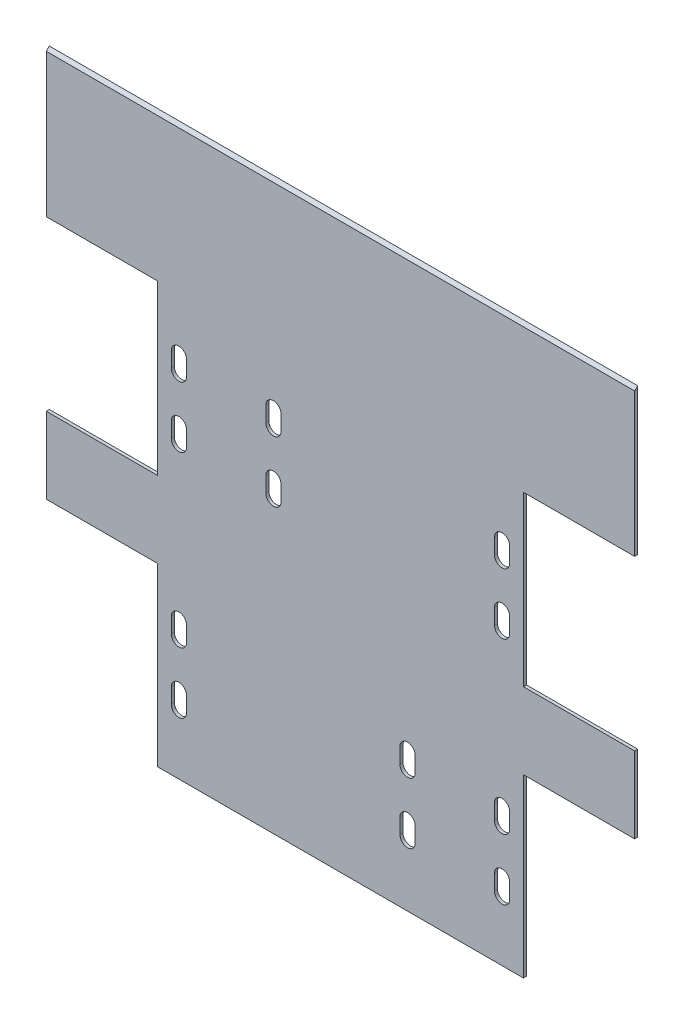
SolidWorks part; units mm, degrees
material "Plain Carbon Steel"
ref_plane "Front Plane" through (0, 0, 0) normal (0, 0, 1) x (1, 0, 0)
ref_plane "Top Plane" through (0, 0, 0) normal (0, 1, 0) x (1, 0, 0)
ref_plane "Right Plane" through (0, 0, 0) normal (1, 0, 0) x (0, 0, -1)
sketch "Sketch1" plane through (0, 0, 0) normal (0, 0, 1) x (1, 0, 0)
  line L1 (-96.5, 72.5) -> (96.5, 72.5)
  line L2 (-96.5, 72.5) -> (-96.5, -72.5)
  line L3 (-96.5, -72.5) -> (96.5, -72.5)
  line L4 (96.5, 72.5) -> (96.5, -72.5)
  line L5 (-96.5, 72.5) -> (96.5, -72.5) construction
  line L6 (-96.5, -72.5) -> (96.5, 72.5) construction
  line L7 (-95, 65.5) -> (-60, 65.5)
  line L8 (-95, 65.5) -> (-95, 5.5)
  line L9 (-95, 5.5) -> (-60, 5.5)
  line L10 (-60, 65.5) -> (-60, 5.5)
  line L11 (-95, 65.5) -> (-60, 5.5) construction
  line L12 (-95, 5.5) -> (-60, 65.5) construction
  line L13 (60, 65.5) -> (95, 65.5)
  line L14 (60, 65.5) -> (60, 5.5)
  line L15 (60, 5.5) -> (95, 5.5)
  line L16 (95, 65.5) -> (95, 5.5)
  line L17 (60, 65.5) -> (95, 5.5) construction
  line L18 (60, 5.5) -> (95, 65.5) construction
  line L19 (60, -9.5) -> (95, -9.5)
  line L20 (60, -9.5) -> (60, -69.5)
  line L21 (60, -69.5) -> (95, -69.5)
  line L22 (95, -9.5) -> (95, -69.5)
  line L23 (60, -9.5) -> (95, -69.5) construction
  line L24 (60, -69.5) -> (95, -9.5) construction
  line L25 (-95, -9.5) -> (-60, -9.5)
  line L26 (-95, -9.5) -> (-95, -69.5)
  line L27 (-95, -69.5) -> (-60, -69.5)
  line L28 (-60, -9.5) -> (-60, -69.5)
  line L29 (-95, -9.5) -> (-60, -69.5) construction
  line L30 (-95, -69.5) -> (-60, -9.5) construction
  point P0 (0, 0)
  point P6 (-77.5, 35.5)
  point P11 (77.5, 35.5)
  point P16 (77.5, -39.5)
  point P21 (-77.5, -39.5)
  dimension "D1" = 193
  dimension "D2" = 145
  dimension "D3" = 35
  dimension "D4" = 35
  dimension "D5" = 35
  dimension "D6" = 35
  dimension "D7" = 60
  dimension "D8" = 60
  dimension "D9" = 60
  dimension "D10" = 60
  dimension "D11" = 19
  dimension "D12" = 19
  dimension "D13" = 15
  dimension "D14" = 33
  dimension "D15" = 19
  dimension "D16" = 19
  dimension "D17" = 33
  dimension "D18" = 15
  dimension "D19" = 145
extrude "Boss-Extrude1" add sketch "Sketch1" along normal blind 1
sketch "Sketch2" plane through (0, 0, 1) normal (0, 0, 1) x (1, 0, 0)
  line L0 (-60, 5.5) -> (-60, 65.5) construction
  line L1 (-60, 65.5) -> (-95, 65.5) construction
  line L2 (-95, -69.5) -> (-60, -69.5) construction
  line L3 (0, 72.5) -> (0, -72.5) construction
  line L4 (96.5, 72.5) -> (-96.5, 72.5) construction
  line L7 (-96.5, -72.5) -> (96.5, -72.5) construction
  line L8 (-60, -69.5) -> (-60, -9.5) construction
  circle A0 centre (-53, 45.5) radius 2.5
  circle A1 centre (-53, 25.5) radius 2.5
  circle A4 centre (-53, -49.5) radius 2.5
  circle A5 centre (-53, -29.5) radius 2.5
  circle A6 centre (53, -29.5) radius 2.5
  circle A7 centre (53, -49.5) radius 2.5
  circle A8 centre (53, 25.5) radius 2.5
  circle A9 centre (53, 45.5) radius 2.5
  dimension "D1" = 5
  dimension "D2" = 5
  dimension "D7" = 5
  dimension "D8" = 5
  dimension "D3" = 7
  dimension "D4" = 7
  dimension "D5" = 20
  dimension "D6" = 20
  dimension "D9" = 20
  dimension "D10" = 20
  dimension "D11" = 7
  dimension "D12" = 7
extrude "Cut-Extrude1" cut sketch "Sketch2" against normal blind 3
sketch "Sketch3" plane through (0, 0, 1) normal (0, 0, 1) x (1, 0, 0)
  line L0 (-96.5, 72.5) -> (-96.5, -72.5) construction
  line L1 (-95, 65.5) -> (-96.5, 65.5)
  line L2 (-95, 65.5) -> (-95, 5.3442)
  line L3 (-95, 5.3442) -> (-96.5, 5.3442)
  line L4 (-96.5, 65.5) -> (-96.5, 5.3442)
  line L5 (96.5, -72.5) -> (96.5, 72.5) construction
  line L6 (-95, -69.5) -> (-96.5, -69.5)
  line L7 (-95, -69.5) -> (-95, -9.5)
  line L8 (-95, -9.5) -> (-96.5, -9.5)
  line L9 (-96.5, -69.5) -> (-96.5, -9.5)
  line L10 (95, -9.5) -> (96.5, -9.5)
  line L11 (95, -9.5) -> (95, -69.5)
  line L12 (95, -69.5) -> (96.5, -69.5)
  line L13 (96.5, -9.5) -> (96.5, -69.5)
  line L15 (95, 65.5) -> (96.5, 65.5)
  line L16 (95, 65.5) -> (95, 5.5)
  line L17 (95, 5.5) -> (96.5, 5.5)
  line L18 (96.5, 65.5) -> (96.5, 5.5)
extrude "Cut-Extrude2" cut sketch "Sketch3" against normal blind 3
sketch "Sketch4" plane through (0, 0, 1) normal (0, 0, 1) x (1, 0, 0)
  line L1 (-96.5, 72.5) -> (96.5, 72.5)
  line L2 (-96.5, 72.5) -> (-96.5, 114.5)
  line L3 (-96.5, 114.5) -> (96.5, 114.5)
  line L4 (96.5, 72.5) -> (96.5, 114.5)
  dimension "D1" = 42
  dimension "D2" = 193
extrude "Boss-Extrude2" add sketch "Sketch4" against normal blind 1
sketch "Sketch5" plane through (-96.5, 0, 0) normal (-1, 0, 0) x (0, 0, 1)
  line L0 (1, -69.5) -> (1, -9.5) construction
  line L1 (0, 10.2591) -> (1, 10.2591)
  line L2 (0, 10.2591) -> (0, -14.7409)
  line L3 (0, -14.7409) -> (1, -14.7409)
  line L4 (1, 10.2591) -> (1, -14.7409)
  line L5 (0, 10.2591) -> (1, -14.7409) construction
  line L6 (0, -14.7409) -> (1, 10.2591) construction
  point P0 (0.5, -2.2409)
  dimension "D1" = 25
extrude "Boss-Extrude3" add sketch "Sketch5" against normal blind 194
chamfer "Chamfer1" distance 2 angle 45 1 edges at (0, 114.5, 1)
sketch "Sketch7" plane through (0, 0, 1) normal (0, 0, 1) x (1, 0, 0)
  line L0 (-96.5, -72.5) -> (96.5, -72.5) construction
  line L1 (-96.5, -69.5) -> (-60, -69.5)
  line L2 (-96.5, -69.5) -> (-96.5, -72.5)
  line L3 (-96.5, -72.5) -> (-60, -72.5)
  line L4 (-60, -69.5) -> (-60, -72.5)
  line L6 (96.5, -69.5) -> (60, -69.5)
  line L7 (96.5, -69.5) -> (96.5, -72.5)
  line L8 (96.5, -72.5) -> (60, -72.5)
  line L9 (60, -69.5) -> (60, -72.5)
extrude "Cut-Extrude3" cut sketch "Sketch7" against normal blind 10
sketch "Sketch8" plane through (0, 0, 1) normal (0, 0, 1) x (1, 0, 0)
  circle A0 centre (-22, 45.5) radius 2.5
  circle A1 centre (-22, 25.5) radius 2.5
  circle A2 centre (-53, 45.5) radius 2.5 construction
  circle A3 centre (-53, 25.5) radius 2.5 construction
  circle A4 centre (22, -29.5) radius 2.5
  circle A5 centre (22, -49.5) radius 2.5
  circle A6 centre (53, -29.5) radius 2.5 construction
  circle A7 centre (53, -49.5) radius 2.5 construction
  dimension "D1" = 5
  dimension "D2" = 5
  dimension "D3" = 31
  dimension "D4" = 31
  dimension "D5" = 5
  dimension "D6" = 5
  dimension "D8" = 31
  dimension "D7" = 31
extrude "Cut-Extrude4" cut sketch "Sketch8" against normal blind 10
sketch "Sketch11" plane through (97.5, 0, 0) normal (1, 0, 0) x (0, 0, -1)
  line L1 (-1, 10.2591) -> (0, 10.2591)
  line L2 (-1, 10.2591) -> (-1, -14.7409)
  line L3 (-1, -14.7409) -> (0, -14.7409)
  line L4 (0, 10.2591) -> (0, -14.7409)
extrude "Cut-Extrude5" cut sketch "Sketch11" against normal blind 1
sketch "Sketch12" plane through (0, 0, 1) normal (0, 0, 1) x (1, 0, 0)
  line L0 (-53, 48) -> (-53, 43) construction
  line L1 (-50.5, 48) -> (-50.5, 43)
  line L2 (-55.5, 48) -> (-55.5, 43)
  line L3 (-22, 48) -> (-22, 43) construction
  line L4 (-19.5, 48) -> (-19.5, 43)
  line L5 (-24.5, 48) -> (-24.5, 43)
  line L6 (-22, 28) -> (-22, 23) construction
  line L7 (-19.5, 28) -> (-19.5, 23)
  line L8 (-24.5, 28) -> (-24.5, 23)
  line L9 (-53, 28) -> (-53, 23) construction
  line L10 (-50.5, 28) -> (-50.5, 23)
  line L11 (-55.5, 28) -> (-55.5, 23)
  line L12 (-96.5, -2.2409) -> (96.5, -2.2409) construction
  line L14 (53, 28) -> (53, 23) construction
  line L15 (50.5, 28) -> (50.5, 23)
  line L16 (55.5, 28) -> (55.5, 23)
  line L17 (53, 48) -> (53, 43) construction
  line L18 (50.5, 48) -> (50.5, 43)
  line L19 (55.5, 48) -> (55.5, 43)
  line L20 (-96.5, 10.2591) -> (-96.5, -14.7409) construction
  line L21 (96.5, 10.2591) -> (96.5, -14.7409) construction
  line L22 (53, -52.4818) -> (53, -47.4818) construction
  line L23 (50.5, -52.4818) -> (50.5, -47.4818)
  line L24 (55.5, -52.4818) -> (55.5, -47.4818)
  line L25 (53, -32.4818) -> (53, -27.4818) construction
  line L26 (50.5, -32.4818) -> (50.5, -27.4818)
  line L27 (55.5, -32.4818) -> (55.5, -27.4818)
  line L28 (-53, -32.4818) -> (-53, -27.4818) construction
  line L29 (-50.5, -32.4818) -> (-50.5, -27.4818)
  line L30 (-55.5, -32.4818) -> (-55.5, -27.4818)
  line L31 (-53, -52.4818) -> (-53, -47.4818) construction
  line L32 (-50.5, -52.4818) -> (-50.5, -47.4818)
  line L33 (-55.5, -52.4818) -> (-55.5, -47.4818)
  line L34 (22, -27) -> (22, -32) construction
  line L35 (24.5, -27) -> (24.5, -32)
  line L36 (19.5, -27) -> (19.5, -32)
  line L37 (22, -47) -> (22, -52) construction
  line L38 (24.5, -47) -> (24.5, -52)
  line L39 (19.5, -47) -> (19.5, -52)
  arc A0 (-50.5, 48) -> (-55.5, 48) centre (-53, 48) ccw
  arc A1 (-55.5, 43) -> (-50.5, 43) centre (-53, 43) ccw
  arc A2 (-19.5, 48) -> (-24.5, 48) centre (-22, 48) ccw
  arc A3 (-24.5, 43) -> (-19.5, 43) centre (-22, 43) ccw
  arc A4 (-19.5, 28) -> (-24.5, 28) centre (-22, 28) ccw
  arc A5 (-24.5, 23) -> (-19.5, 23) centre (-22, 23) ccw
  arc A6 (-50.5, 28) -> (-55.5, 28) centre (-53, 28) ccw
  arc A7 (-55.5, 23) -> (-50.5, 23) centre (-53, 23) ccw
  arc A8 (50.5, 28) -> (55.5, 28) centre (53, 28) cw
  arc A9 (55.5, 23) -> (50.5, 23) centre (53, 23) cw
  arc A10 (50.5, 48) -> (55.5, 48) centre (53, 48) cw
  arc A11 (55.5, 43) -> (50.5, 43) centre (53, 43) cw
  arc A12 (50.5, -52.4818) -> (55.5, -52.4818) centre (53, -52.4818) ccw
  arc A13 (55.5, -47.4818) -> (50.5, -47.4818) centre (53, -47.4818) ccw
  arc A14 (50.5, -32.4818) -> (55.5, -32.4818) centre (53, -32.4818) ccw
  arc A15 (55.5, -27.4818) -> (50.5, -27.4818) centre (53, -27.4818) ccw
  arc A16 (-50.5, -32.4818) -> (-55.5, -32.4818) centre (-53, -32.4818) cw
  arc A17 (-55.5, -27.4818) -> (-50.5, -27.4818) centre (-53, -27.4818) cw
  arc A18 (-50.5, -52.4818) -> (-55.5, -52.4818) centre (-53, -52.4818) cw
  arc A19 (-55.5, -47.4818) -> (-50.5, -47.4818) centre (-53, -47.4818) cw
  arc A20 (24.5, -27) -> (19.5, -27) centre (22, -27) ccw
  arc A21 (19.5, -32) -> (24.5, -32) centre (22, -32) ccw
  arc A22 (24.5, -47) -> (19.5, -47) centre (22, -47) ccw
  arc A23 (19.5, -52) -> (24.5, -52) centre (22, -52) ccw
  point P2 (-53, 45.5)
  point P9 (-22, 45.5)
  point P17 (-22, 25.5)
  point P25 (-53, 25.5)
  point P39 (53, 25.5)
  point P46 (53, 45.5)
  point P55 (53, -49.9818)
  point P62 (53, -29.9818)
  point P69 (-53, -29.9818)
  point P76 (-53, -49.9818)
  point P83 (22, -29.5)
  point P90 (22, -49.5)
  dimension "D2" = 2.5
  dimension "D4" = 2.5
  dimension "D5" = 2.5
  dimension "D7" = 2.5
  dimension "D9" = 5
  dimension "D10" = 2.5
  dimension "D11" = 2.5
  dimension "D1" = 5
  dimension "D3" = 5
  dimension "D6" = 5
  dimension "D8" = 5
  dimension "D12" = 5
extrude "Cut-Extrude6" cut sketch "Sketch12" against normal blind 10
